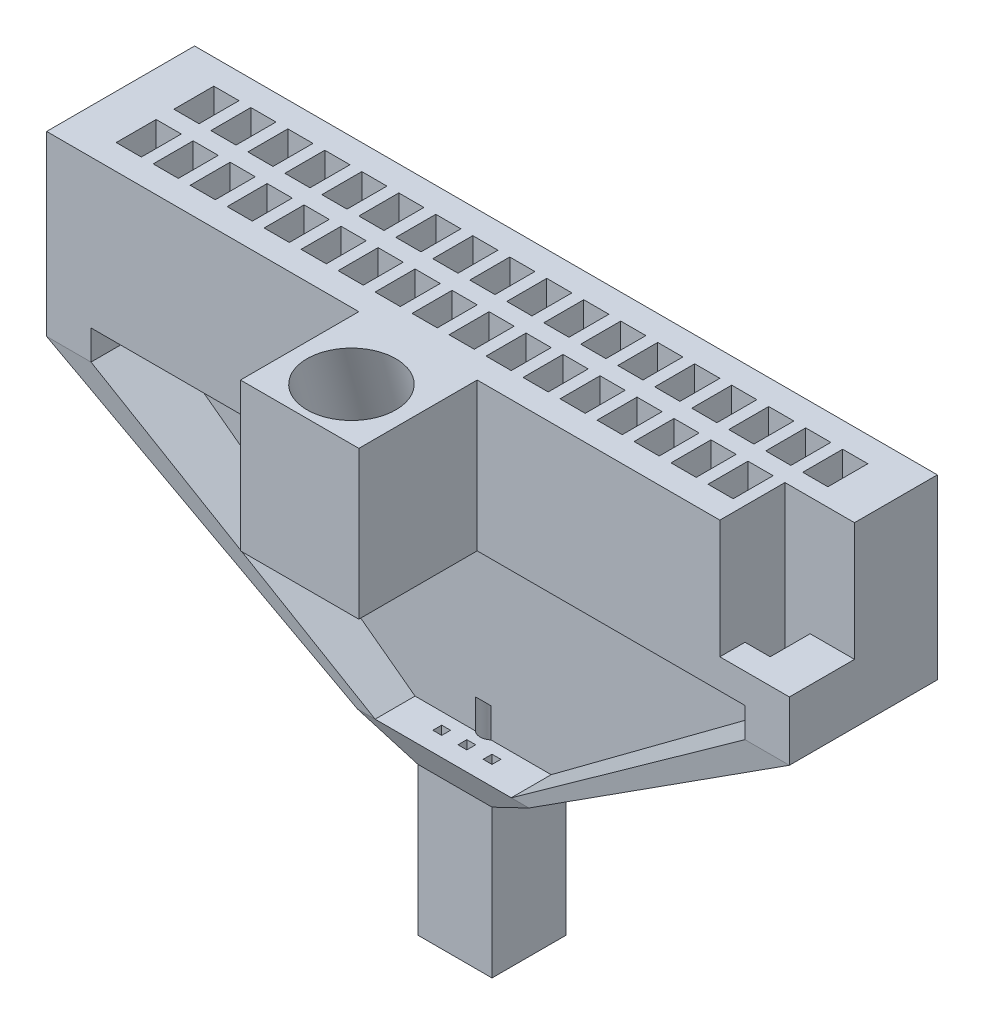
SolidWorks part; units mm, degrees
note: The reader was unsure of these and kept them because the rebuilt part matched: shared geometry of "Sketch13<3>".
ref_plane "Front Plane" through (0, 0, 0) normal (0, 0, 1) x (1, 0, 0)
ref_plane "Top Plane" through (0, 0, 0) normal (0, 1, 0) x (1, 0, 0)
ref_plane "Right Plane" through (0, 0, 0) normal (1, 0, 0) x (0, 0, -1)
sketch "main_block" plane through (0, 0, 0) normal (0, 1, 0) x (1, 0, 0)
  line L1 (-5.6188, 1.2192) -> (7.132, 1.2192)
  line L2 (-5.6188, 1.2192) -> (-5.6188, -1.3208)
  line L3 (-5.6188, -1.3208) -> (7.132, -1.3208)
  line L4 (7.132, 1.2192) -> (7.132, -1.3208)
  dimension "D1" = 12.7508
  dimension "D2" = 2.54
sketch "top_holes" plane through (0, 0, 0) normal (0, 1, 0) x (1, 0, 0)
  line L0 (7.132, 1.2192) -> (7.132, -1.3208) construction
  line L1 (6.37, 0.7874) -> (5.9382, 0.7874)
  line L2 (6.37, 0.7874) -> (6.37, 0.1016)
  line L3 (6.37, 0.1016) -> (5.9382, 0.1016)
  line L4 (5.9382, 0.7874) -> (5.9382, 0.1016)
  line L5 (-5.6188, 1.2192) -> (7.132, 1.2192) construction
  line L6 (5.3032, 0.7874) -> (5.3032, 0.1016)
  line L7 (5.735, 0.7874) -> (5.3032, 0.7874)
  line L8 (5.735, 0.7874) -> (5.735, 0.1016)
  line L9 (5.735, 0.1016) -> (5.3032, 0.1016)
  line L10 (4.6682, 0.7874) -> (4.6682, 0.1016)
  line L11 (5.1, 0.7874) -> (4.6682, 0.7874)
  line L12 (5.1, 0.7874) -> (5.1, 0.1016)
  line L13 (5.1, 0.1016) -> (4.6682, 0.1016)
  line L14 (4.0332, 0.7874) -> (4.0332, 0.1016)
  line L15 (4.465, 0.7874) -> (4.0332, 0.7874)
  line L16 (4.465, 0.7874) -> (4.465, 0.1016)
  line L17 (4.465, 0.1016) -> (4.0332, 0.1016)
  line L18 (3.3982, 0.7874) -> (3.3982, 0.1016)
  line L19 (3.83, 0.7874) -> (3.3982, 0.7874)
  line L20 (3.83, 0.7874) -> (3.83, 0.1016)
  line L21 (3.83, 0.1016) -> (3.3982, 0.1016)
  line L22 (2.7632, 0.7874) -> (2.7632, 0.1016)
  line L23 (3.195, 0.7874) -> (2.7632, 0.7874)
  line L24 (3.195, 0.7874) -> (3.195, 0.1016)
  line L25 (3.195, 0.1016) -> (2.7632, 0.1016)
  line L26 (2.1282, 0.7874) -> (2.1282, 0.1016)
  line L27 (2.56, 0.7874) -> (2.1282, 0.7874)
  line L28 (2.56, 0.7874) -> (2.56, 0.1016)
  line L29 (2.56, 0.1016) -> (2.1282, 0.1016)
  line L30 (1.4932, 0.7874) -> (1.4932, 0.1016)
  line L31 (1.925, 0.7874) -> (1.4932, 0.7874)
  line L32 (1.925, 0.7874) -> (1.925, 0.1016)
  line L33 (1.925, 0.1016) -> (1.4932, 0.1016)
  line L34 (0.8582, 0.7874) -> (0.8582, 0.1016)
  line L35 (1.29, 0.7874) -> (0.8582, 0.7874)
  line L36 (1.29, 0.7874) -> (1.29, 0.1016)
  line L37 (1.29, 0.1016) -> (0.8582, 0.1016)
  line L38 (0.2232, 0.7874) -> (0.2232, 0.1016)
  line L39 (0.655, 0.7874) -> (0.2232, 0.7874)
  line L40 (0.655, 0.7874) -> (0.655, 0.1016)
  line L41 (0.655, 0.1016) -> (0.2232, 0.1016)
  line L42 (-0.4117, 0.7874) -> (-0.4117, 0.1016)
  line L43 (0.0201, 0.7874) -> (-0.4117, 0.7874)
  line L44 (0.0201, 0.7874) -> (0.0201, 0.1016)
  line L45 (0.0201, 0.1016) -> (-0.4117, 0.1016)
  line L46 (-1.0467, 0.7874) -> (-1.0467, 0.1016)
  line L47 (-0.6149, 0.7874) -> (-1.0467, 0.7874)
  line L48 (-0.6149, 0.7874) -> (-0.6149, 0.1016)
  line L49 (-0.6149, 0.1016) -> (-1.0467, 0.1016)
  line L50 (-1.6817, 0.7874) -> (-1.6817, 0.1016)
  line L51 (-1.2499, 0.7874) -> (-1.6817, 0.7874)
  line L52 (-1.2499, 0.7874) -> (-1.2499, 0.1016)
  line L53 (-1.2499, 0.1016) -> (-1.6817, 0.1016)
  line L54 (-2.3167, 0.7874) -> (-2.3167, 0.1016)
  line L55 (-1.8849, 0.7874) -> (-2.3167, 0.7874)
  line L56 (-1.8849, 0.7874) -> (-1.8849, 0.1016)
  line L57 (-1.8849, 0.1016) -> (-2.3167, 0.1016)
  line L58 (-2.9517, 0.7874) -> (-2.9517, 0.1016)
  line L59 (-2.5199, 0.7874) -> (-2.9517, 0.7874)
  line L60 (-2.5199, 0.7874) -> (-2.5199, 0.1016)
  line L61 (-2.5199, 0.1016) -> (-2.9517, 0.1016)
  line L62 (-3.5867, 0.7874) -> (-3.5867, 0.1016)
  line L63 (-3.1549, 0.7874) -> (-3.5867, 0.7874)
  line L64 (-3.1549, 0.7874) -> (-3.1549, 0.1016)
  line L65 (-3.1549, 0.1016) -> (-3.5867, 0.1016)
  line L66 (-4.2217, 0.7874) -> (-4.2217, 0.1016)
  line L67 (-3.7899, 0.7874) -> (-4.2217, 0.7874)
  line L68 (-3.7899, 0.7874) -> (-3.7899, 0.1016)
  line L69 (-3.7899, 0.1016) -> (-4.2217, 0.1016)
  line L70 (-4.8567, 0.7874) -> (-4.8567, 0.1016)
  line L71 (-4.4249, 0.7874) -> (-4.8567, 0.7874)
  line L72 (-4.4249, 0.7874) -> (-4.4249, 0.1016)
  line L73 (-4.4249, 0.1016) -> (-4.8567, 0.1016)
  line L74 (5.3032, -0.2032) -> (5.3032, -0.889)
  line L75 (5.735, -0.2032) -> (5.3032, -0.2032)
  line L76 (5.735, -0.2032) -> (5.735, -0.889)
  line L77 (5.735, -0.889) -> (5.3032, -0.889)
  line L78 (4.6682, -0.2032) -> (4.6682, -0.889)
  line L79 (5.1, -0.2032) -> (4.6682, -0.2032)
  line L80 (5.1, -0.2032) -> (5.1, -0.889)
  line L81 (5.1, -0.889) -> (4.6682, -0.889)
  line L82 (4.0332, -0.2032) -> (4.0332, -0.889)
  line L83 (4.465, -0.2032) -> (4.0332, -0.2032)
  line L84 (4.465, -0.2032) -> (4.465, -0.889)
  line L85 (4.465, -0.889) -> (4.0332, -0.889)
  line L86 (3.3982, -0.2032) -> (3.3982, -0.889)
  line L87 (3.83, -0.2032) -> (3.3982, -0.2032)
  line L88 (3.83, -0.2032) -> (3.83, -0.889)
  line L89 (3.83, -0.889) -> (3.3982, -0.889)
  line L90 (2.7632, -0.2032) -> (2.7632, -0.889)
  line L91 (3.195, -0.2032) -> (2.7632, -0.2032)
  line L92 (3.195, -0.2032) -> (3.195, -0.889)
  line L93 (3.195, -0.889) -> (2.7632, -0.889)
  line L94 (2.1282, -0.2032) -> (2.1282, -0.889)
  line L95 (2.56, -0.2032) -> (2.1282, -0.2032)
  line L96 (2.56, -0.2032) -> (2.56, -0.889)
  line L97 (2.56, -0.889) -> (2.1282, -0.889)
  line L98 (1.4932, -0.2032) -> (1.4932, -0.889)
  line L99 (1.925, -0.2032) -> (1.4932, -0.2032)
  line L100 (1.925, -0.2032) -> (1.925, -0.889)
  line L101 (1.925, -0.889) -> (1.4932, -0.889)
  line L102 (0.8582, -0.2032) -> (0.8582, -0.889)
  line L103 (1.29, -0.2032) -> (0.8582, -0.2032)
  line L104 (1.29, -0.2032) -> (1.29, -0.889)
  line L105 (1.29, -0.889) -> (0.8582, -0.889)
  line L106 (0.2232, -0.2032) -> (0.2232, -0.889)
  line L107 (0.655, -0.2032) -> (0.2232, -0.2032)
  line L108 (0.655, -0.2032) -> (0.655, -0.889)
  line L109 (0.655, -0.889) -> (0.2232, -0.889)
  line L110 (-0.4117, -0.2032) -> (-0.4117, -0.889)
  line L111 (0.0201, -0.2032) -> (-0.4117, -0.2032)
  line L112 (0.0201, -0.2032) -> (0.0201, -0.889)
  line L113 (0.0201, -0.889) -> (-0.4117, -0.889)
  line L114 (-1.0467, -0.2032) -> (-1.0467, -0.889)
  line L115 (-0.6149, -0.2032) -> (-1.0467, -0.2032)
  line L116 (-0.6149, -0.2032) -> (-0.6149, -0.889)
  line L117 (-0.6149, -0.889) -> (-1.0467, -0.889)
  line L118 (-1.6817, -0.2032) -> (-1.6817, -0.889)
  line L119 (-1.2499, -0.2032) -> (-1.6817, -0.2032)
  line L120 (-1.2499, -0.2032) -> (-1.2499, -0.889)
  line L121 (-1.2499, -0.889) -> (-1.6817, -0.889)
  line L122 (-2.3167, -0.2032) -> (-2.3167, -0.889)
  line L123 (-1.8849, -0.2032) -> (-2.3167, -0.2032)
  line L124 (-1.8849, -0.2032) -> (-1.8849, -0.889)
  line L125 (-1.8849, -0.889) -> (-2.3167, -0.889)
  line L126 (-2.9517, -0.2032) -> (-2.9517, -0.889)
  line L127 (-2.5199, -0.2032) -> (-2.9517, -0.2032)
  line L128 (-2.5199, -0.2032) -> (-2.5199, -0.889)
  line L129 (-2.5199, -0.889) -> (-2.9517, -0.889)
  line L130 (-3.5867, -0.2032) -> (-3.5867, -0.889)
  line L131 (-3.1549, -0.2032) -> (-3.5867, -0.2032)
  line L132 (-3.1549, -0.2032) -> (-3.1549, -0.889)
  line L133 (-3.1549, -0.889) -> (-3.5867, -0.889)
  line L134 (-4.2217, -0.2032) -> (-4.2217, -0.889)
  line L135 (-3.7899, -0.2032) -> (-4.2217, -0.2032)
  line L136 (-3.7899, -0.2032) -> (-3.7899, -0.889)
  line L137 (-3.7899, -0.889) -> (-4.2217, -0.889)
  line L138 (-4.8567, -0.2032) -> (-4.8567, -0.889)
  line L139 (-4.4249, -0.2032) -> (-4.8567, -0.2032)
  line L140 (-4.4249, -0.2032) -> (-4.4249, -0.889)
  line L141 (-4.4249, -0.889) -> (-4.8567, -0.889)
  line L142 (5.9382, -0.2032) -> (5.9382, -0.889)
  line L143 (6.37, -0.2032) -> (5.9382, -0.2032)
  line L144 (6.37, -0.2032) -> (6.37, -0.889)
  line L145 (6.37, -0.889) -> (5.9382, -0.889)
  line L148 (-5.6188, 1.2192) -> (-5.6188, -1.3208) construction
  dimension "D1" = 0.4318
  dimension "D2" = 0.6858
  dimension "D3" = 0.762
  dimension "D4" = 0.4318
  dimension "D5" = 18
  dimension "D6" = 2
extrude "well_block" add sketch "main_block" against normal blind 2.54
extrude "omnetics_wells" cut sketch "top_holes" against normal blind 2.54
ref_plane "Plane1" through (0, -6.35, 0) normal (0, 1, 0) x (1, 0, 0)
sketch "Sketch4" plane through (0, -6.35, 0) normal (0, 1, 0) x (1, 0, 0)
  line L1 (1.9249, 0.889) -> (-0.4117, 0.889)
  line L2 (1.9249, 0.889) -> (1.9249, -0.889)
  line L3 (1.9249, -0.889) -> (-0.4117, -0.889)
  line L4 (-0.4117, 0.889) -> (-0.4117, -0.889)
  line L5 (1.9249, 0.889) -> (-0.4117, -0.889) construction
  line L6 (1.9249, -0.889) -> (-0.4117, 0.889) construction
  point P0 (0.7566, 0)
  dimension "D1" = 2.3367
  dimension "D2" = 1.778
sketch "Sketch5" plane through (0, -2.54, 0) normal (0, -1, 0) x (1, 0, 0)
  line L1 (-4.8567, 0.2032) -> (6.37, 0.2032)
  line L2 (-4.8567, 0.2032) -> (-4.8567, -0.1016)
  line L3 (-4.8567, -0.1016) -> (6.37, -0.1016)
  line L4 (6.37, 0.2032) -> (6.37, -0.1016)
sketch "Sketch6" plane through (0, -6.35, 0) normal (0, 1, 0) x (1, 0, 0)
  line L1 (-0.4117, 0.1016) -> (1.925, 0.1016)
  line L2 (-0.4117, 0.1016) -> (-0.4117, -0.2032)
  line L3 (-0.4117, -0.2032) -> (1.925, -0.2032)
  line L4 (1.925, 0.1016) -> (1.925, -0.2032)
sketch "Sketch7" plane through (0, -6.35, 0) normal (0, 1, 0) x (1, 0, 0)
  line L0 (-0.4117, -0.889) -> (-0.4117, 0.889)
  line L1 (-0.4117, -0.889) -> (-0.7165, -0.889)
  line L2 (-0.4117, 0.889) -> (-0.7165, 0.889)
  line L3 (-0.7165, -0.889) -> (-0.7165, 0.889)
  dimension "D1" = 0.3048
sketch "Sketch8" plane through (0, -2.54, 0) normal (0, -1, 0) x (1, 0, 0)
  line L0 (-4.8567, 1.3208) -> (-4.8567, -1.2192)
  line L1 (-4.8567, 1.3208) -> (-5.6187, 1.3208)
  line L2 (-4.8567, -1.2192) -> (-5.6187, -1.2192)
  line L3 (-5.6187, 1.3208) -> (-5.6187, -1.2192)
  line L4 (-5.6188, 1.3208) -> (7.132, 1.3208) construction
  line L5 (7.132, -1.2192) -> (-5.6188, -1.2192) construction
  dimension "D1" = 0.762
  dimension "D2" = 0
  dimension "D3" = 0
extrude "supportbeam1" add sketch "Sketch8" along normal blind 0.508
sketch "Sketch9" plane through (0, -6.35, 0) normal (0, 1, 0) x (1, 0, 0)
  line L0 (1.925, -0.889) -> (1.9249, 0.889)
  line L1 (1.925, -0.889) -> (2.2298, -0.889)
  line L2 (1.9249, 0.889) -> (2.2297, 0.889)
  line L3 (2.2298, -0.889) -> (2.2297, 0.889)
  dimension "D1" = 0.3048
sketch "Sketch10" plane through (0, -2.54, 0) normal (0, -1, 0) x (1, 0, 0)
  line L0 (6.37, -1.2192) -> (6.37, 1.3208)
  line L1 (6.37, -1.2192) -> (7.132, -1.2192)
  line L2 (6.37, 1.3208) -> (7.132, 1.3208)
  line L3 (7.132, -1.2192) -> (7.132, 1.3208)
  line L4 (-5.6188, 1.3208) -> (-5.6187, 1.3208) construction
  line L5 (7.132, -1.2192) -> (-4.8567, -1.2192) construction
  dimension "D1" = 0.762
  dimension "D2" = 0
  dimension "D3" = 0
extrude "supportbeam2" add sketch "Sketch10" along normal blind 0.508
loft "arm1" add profiles "Sketch9" section "Sketch9" section face at (6.751, -3.048, 0.0508) connector at (1.925, -6.35, 0.889) connector at (6.37, -3.048, 1.3208)
loft "arm2" add profiles "Sketch7" section "Sketch7" section face at (-5.2377, -3.048, 0.0508) connector at (-0.4117, -6.35, 0.889) connector at (-4.8567, -3.048, 1.3208)
extrude "wall_divider" add sketch "Sketch5" along normal blind 0.508
loft "wall_divider2" add profiles "Sketch6" section face at (0.7566, -3.048, 0.0508) section "Sketch6" connector at (-4.8567, -3.048, -0.1016) connector at (-0.4117, -6.35, -0.1016)
sketch "Sketch12" plane through (0, -6.35, 0) normal (0, 1, 0) x (1, 0, 0)
  line L1 (-0.7165, 0.889) -> (2.2299, 0.889)
  line L2 (-0.7165, 0.889) -> (-0.7165, -0.889)
  line L3 (-0.7165, -0.889) -> (2.2299, -0.889)
  line L4 (2.2299, 0.889) -> (2.2299, -0.889)
  line L6 (-0.4117, 0.889) -> (-0.7165, 0.889) construction
  line L7 (-0.7165, -0.889) -> (-0.4117, -0.889) construction
  dimension "D1" = 0
  dimension "D2" = 2.9464
  dimension "D3" = 0
ref_plane "Plane2" through (0, -6.858, 0) normal (0, 1, 0) x (1, 0, 0)
sketch "Sketch13" plane through (0, -6.858, 0) normal (0, 1, 0) x (1, 0, 0)
  line L0 (0.8582, -0.2032) -> (0.8582, -0.889) construction
  line L1 (1.3916, 0.5842) -> (0.1216, 0.5842)
  line L2 (1.3916, 0.5842) -> (1.3916, -0.6858)
  line L3 (1.3916, -0.6858) -> (0.1216, -0.6858)
  line L4 (0.1216, 0.5842) -> (0.1216, -0.6858)
  line L5 (1.3916, 0.5842) -> (0.1216, -0.6858) construction
  line L6 (1.3916, -0.6858) -> (0.1216, 0.5842) construction
  line L7 (0.655, -0.889) -> (0.655, -0.2032) construction
  line L8 (6.37, -0.2032) -> (1.925, -0.2032) construction
  line L9 (1.925, 0.1016) -> (6.37, 0.1016) construction
  point P0 (0.7566, 0)
  dimension "D1" = 1.27
  dimension "D2" = 1.27
  dimension "D3" = 0.4826
  dimension "D4" = 0.5334
  dimension "D5" = 0.5334
  dimension "D6" = 0.4826
loft "exit_base" add profiles "Sketch12", "Sketch13" connector at (2.2299, -6.35, -0.889) connector at (1.3916, -6.858, -0.5842)
extrude "tetrode_funnel" add sketch "Sketch13<3>" against normal blind 2.54
sketch "Sketch13<3>" plane through (0, -6.858, 0) normal (0, 1, 0) x (1, 0, 0) same geometry as "Sketch13"
sketch "Sketch17" plane through (0, 0, 0) normal (0, 1, 0) x (1, 0, 0)
  line L1 (5.9382, -0.2032) -> (7.132, -0.2032)
  line L2 (5.9382, -0.2032) -> (5.9382, -1.3208)
  line L3 (5.9382, -1.3208) -> (7.132, -1.3208)
  line L4 (7.132, -0.2032) -> (7.132, -1.3208)
extrude "ground_wire_hole" cut sketch "Sketch17" against normal blind 2.032
sketch "Sketch19" plane through (0, -9.398, 0) normal (0, -1, 0) x (1, 0, 0)
  line L0 (0.1216, -0.5842) -> (0.1216, 0.6858) construction
  line L1 (0.1216, 0.6858) -> (1.3916, 0.6858) construction
  circle A0 centre (0.7566, 0.0508) radius 0.2032
  point P2 (0.1216, 0.0508)
  dimension "D1" = 0.635
  dimension "D2" = 0.635
extrude "fiber_optic_hole" cut sketch "Sketch19" against normal blind 3.556
sketch "Sketch20" plane through (0, 0, 1.3208) normal (0, 0, 1) x (1, 0, 0)
  line L0 (-4.8567, -2.54) -> (6.37, -2.54) construction
  line L1 (-0.2594, -2.54) -> (1.7726, -2.54)
  line L2 (-0.2594, -2.54) -> (-0.2594, 0)
  line L3 (-0.2594, 0) -> (1.7726, 0)
  line L4 (1.7726, -2.54) -> (1.7726, 0)
  line L5 (-5.6188, -2.54) -> (-5.6188, 0) construction
  line L6 (7.132, -2.032) -> (7.132, 0) construction
  dimension "D1" = 2.54
  dimension "D2" = 2.032
  dimension "D3" = 5.3594
  dimension "D4" = 5.3594
extrude "fiber_optic_holder" add sketch "Sketch20" along normal blind 2.032
sketch "Sketch24" plane through (0, -2.54, 0) normal (0, -1, 0) x (1, 0, 0)
  line L1 (-0.4117, 0.889) -> (1.925, 0.889) construction
  circle A0 centre (0.7606, 1.778) radius 0.762
  dimension "D1" = 0.889
sketch "Sketch25" plane through (0, 0, 0) normal (0, 1, 0) x (1, 0, 0)
  line L0 (1.7726, -3.3528) -> (-0.2594, -3.3528) construction
  circle A0 centre (0.7566, -2.4638) radius 0.762
  dimension "D1" = 0.889
loft "Cut-Loft1" cut profiles "Sketch24", "Sketch25" connector at (0.8724, -2.54, 2.5318) connector at (0.8398, 0, 3.2212)
sketch "tetrode_sketch" plane through (0, -9.398, 0) normal (0, -1, 0) x (1, 0, 0)
  line L0 (0.8328, 0.5588) -> (0.6804, 0.5588)
  line L1 (1.2646, 0.5588) -> (1.1122, 0.5588)
  line L2 (1.2646, 0.5588) -> (1.2646, 0.4064)
  line L3 (1.2646, 0.4064) -> (1.1122, 0.4064)
  line L4 (1.1122, 0.5588) -> (1.1122, 0.4064)
  line L5 (0.8328, 0.5588) -> (0.8328, 0.4064)
  line L6 (0.8328, 0.4064) -> (0.6804, 0.4064)
  line L7 (0.6804, 0.5588) -> (0.6804, 0.4064)
  line L8 (0.401, 0.5588) -> (0.2486, 0.5588)
  line L9 (0.401, 0.5588) -> (0.401, 0.4064)
  line L10 (0.401, 0.4064) -> (0.2486, 0.4064)
  line L11 (0.2486, 0.5588) -> (0.2486, 0.4064)
  line L16 (0.401, 0.127) -> (0.2486, 0.127)
  line L17 (0.401, 0.127) -> (0.401, -0.0254)
  line L18 (0.401, -0.0254) -> (0.2486, -0.0254)
  line L19 (0.2486, 0.127) -> (0.2486, -0.0254)
  line L20 (0.8328, -0.3048) -> (0.6804, -0.3048)
  line L21 (0.8328, -0.3048) -> (0.8328, -0.4572)
  line L22 (0.8328, -0.4572) -> (0.6804, -0.4572)
  line L23 (0.6804, -0.3048) -> (0.6804, -0.4572)
  line L24 (0.401, -0.3048) -> (0.2486, -0.3048)
  line L25 (0.401, -0.3048) -> (0.401, -0.4572)
  line L26 (0.401, -0.4572) -> (0.2486, -0.4572)
  line L27 (0.2486, -0.3048) -> (0.2486, -0.4572)
  line L28 (1.2646, 0.127) -> (1.1122, 0.127)
  line L29 (1.2646, 0.127) -> (1.2646, -0.0254)
  line L30 (1.2646, -0.0254) -> (1.1122, -0.0254)
  line L31 (1.1122, 0.127) -> (1.1122, -0.0254)
  line L32 (1.2646, -0.3048) -> (1.1122, -0.3048)
  line L33 (1.2646, -0.3048) -> (1.2646, -0.4572)
  line L34 (1.2646, -0.4572) -> (1.1122, -0.4572)
  line L35 (1.1122, -0.3048) -> (1.1122, -0.4572)
  line L36 (1.3916, 0.6858) -> (1.3916, -0.5842) construction
  line L37 (0.1216, 0.6858) -> (1.3916, 0.6858) construction
  line L39 (0.8328, 0.127) -> (0.6804, 0.127) [skipped]
  line L40 (0.8328, 0.127) -> (0.8328, -0.0254) [skipped]
  line L41 (0.8328, -0.0254) -> (0.6804, -0.0254) [skipped]
  line L42 (0.6804, 0.127) -> (0.6804, -0.0254) [skipped]
  dimension "D1" = 0.1524
  dimension "D2" = 0.1524
  dimension "D5" = 0.127
  dimension "D6" = 0.127
  dimension "D3" = 3
  dimension "D4" = 3
extrude "Cut-Extrude1" cut sketch "tetrode_sketch" against normal blind 3.556
